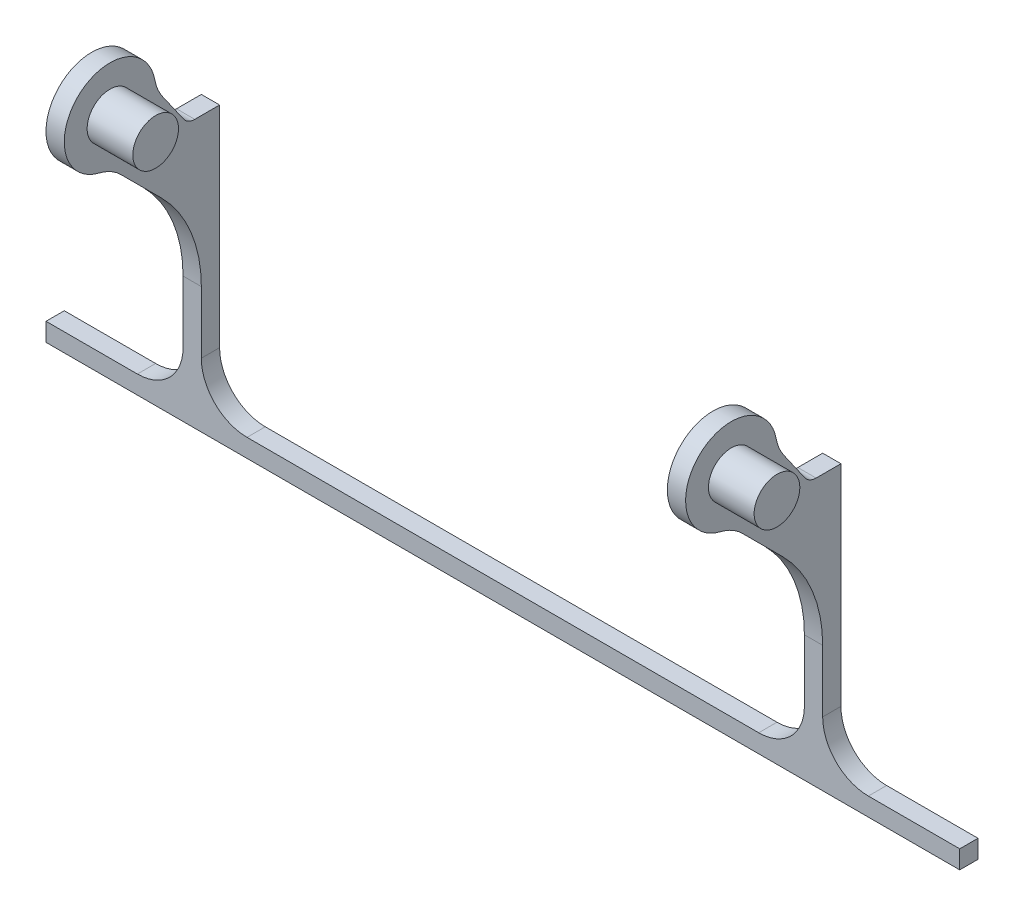
SolidWorks part; units mm, degrees
ref_plane "Plan de face" through (0, 0, 0) normal (0, 0, 1) x (1, 0, 0)
ref_plane "Plan de dessus" through (0, 0, 0) normal (0, 1, 0) x (1, 0, 0)
ref_plane "Plan de droite" through (0, 0, 0) normal (1, 0, 0) x (0, 0, -1)
sketch "Esquisse1" plane through (0, 0, 0) normal (0, 0, 1) x (1, 0, 0)
  line L0 (-100, -100) -> (100, -100) construction
  line L1 (100, -100) -> (100, -160) construction
  line L2 (100, -160) -> (-100, -160) construction
  line L3 (-100, -160) -> (-100, -100) construction
  line L4 (-100, -160) -> (-100, -156) construction
  line L5 (-100, -156) -> (-70, -156) construction
  line L6 (-70, -156) -> (-70, -100) construction
  line L7 (-70, -100) -> (-66, -100) construction
  line L8 (-66, -100) -> (-66, -156) construction
  line L9 (-66, -156) -> (66, -156) construction
  line L10 (66, -156) -> (66, -100) construction
  line L11 (66, -100) -> (70, -100) construction
  line L12 (70, -100) -> (70, -156) construction
  line L13 (70, -156) -> (100, -156) construction
  line L14 (-100, -97.7507) -> (-100, -110) construction
  line L15 (-100, 100) -> (-100, -100) construction
  line L16 (-100, -110) -> (-70, -110) construction
  line L17 (-70, -110) -> (-66, -110) construction
  line L18 (-66, -110) -> (66, -110) construction
  line L19 (66, -110) -> (70, -110) construction
  line L20 (70, -110) -> (100, -110) construction
  line L21 (-70, -110) -> (-66, -110)
  line L22 (-66, -110) -> (-66, -156)
  line L23 (-66, -156) -> (66, -156)
  line L24 (66, -156) -> (66, -110)
  line L25 (66, -110) -> (70, -110)
  line L26 (70, -110) -> (70, -156)
  line L27 (70, -156) -> (100, -156)
  line L28 (100, -156) -> (100, -160)
  line L29 (100, -160) -> (-100, -160)
  line L30 (-100, -160) -> (-100, -156)
  line L31 (-100, -156) -> (-70, -156)
  line L32 (-70, -156) -> (-70, -110)
  dimension "D1" = 4
  dimension "D2" = 4
  dimension "D3" = 4
  dimension "D4" = 4
  dimension "D5" = 4
  dimension "D6" = 30
  dimension "D7" = 30
  dimension "D8" = 10
  dimension "D9" = 60
extrude "Boss.-Extru.1" add sketch "Esquisse1" against normal blind 4
sketch "Esquisse2" plane through (70, 0, 0) normal (1, 0, 0) x (0, 0, -1)
  line L0 (0, -110) -> (-20, -110) construction
  line L1 (-20, -110) -> (-20, -90) construction
  line L2 (4, -110) -> (-10, -90) construction
  line L3 (0, -110) -> (0, -120) construction
  line L4 (0, -156) -> (0, -110) construction
  line L5 (0, -120) -> (-20, -100) construction
  line L6 (0, -120) -> (-20, -100)
  line L7 (4, -110) -> (-10, -90)
  line L8 (0, -120) -> (0, -110)
  line L9 (0, -110) -> (4, -110)
  arc A0 (-10, -90) -> (-20, -100) centre (-20, -90) ccw
  dimension "D3" = 20
  dimension "D1" = 20
  dimension "D2" = 20
  dimension "D4" = 10
extrude "Boss.-Extru.2" add sketch "Esquisse2" against normal blind 4
sketch "Esquisse3" plane through (-70, 0, 0) normal (-1, 0, 0) x (0, 0, 1)
  line L0 (-4, -110) -> (10, -90) construction
  line L1 (20, -100) -> (0, -120) construction
  line L2 (-4, -110) -> (10, -90)
  line L3 (20, -100) -> (0, -120)
  line L4 (-4, -110) -> (0, -110)
  line L5 (0, -110) -> (0, -120)
  arc A0 (20, -100) -> (10, -90) centre (20, -90) ccw construction
  arc A1 (20, -100) -> (10, -90) centre (20, -90) ccw
extrude "Boss.-Extru.3" add sketch "Esquisse3" against normal blind 4
fillet "Congé1" radius 30 2 edges at (68, -120, 0) (-68, -120, 0)
fillet "Congé2" radius 30 2 edges at (-68, -110, -4) (68, -110, -4)
fillet "Congé3" radius 10 4 edges at (66, -156, -2) (-66, -156, -2) (-70, -156, -2) (70, -156, -2)
sketch "Esquisse4" plane through (-70, 0, 0) normal (-1, 0, 0) x (0, 0, 1)
  line L0 (-4, -119.4567) -> (-4, -100)
  line L1 (-4, -100) -> (3, -100)
  line L2 (10, -90) -> (1.423, -102.2528) construction
  line L3 (3, -100) -> (-4, -119.4567)
extrude "Boss.-Extru.4" add sketch "Esquisse4" against normal blind 4
ref_plane "Plan1" through (-66, -100, 3) normal (0, 0, -1) x (-1, 0, 0)
sketch "Esquisse6" plane through (70, 0, 0) normal (1, 0, 0) x (0, 0, -1)
  line L0 (4, -119.4567) -> (4, -100)
  line L1 (4, -100) -> (-3, -100)
  line L2 (-3, -100) -> (4, -119.4567)
extrude "Boss.-Extru.5" add sketch "Esquisse6" against normal blind 4
sketch "Esquisse7" plane through (70, 0, 0) normal (1, 0, 0) x (0, 0, -1)
  line L0 (4, -100) -> (-20, -100) construction
  line L1 (-20, -100) -> (-20, -90) construction
  circle A0 centre (-20, -90) radius 5
  dimension "D1" = 10
extrude "Boss.-Extru.6" add sketch "Esquisse7" along normal blind 10
sketch "Esquisse9" plane through (-70, 0, 0) normal (-1, 0, 0) x (0, 0, 1)
  line L0 (-4, -100) -> (20, -100) construction
  line L1 (20, -100) -> (20, -90) construction
  circle A0 centre (20, -90) radius 5
  dimension "D1" = 10
extrude "Boss.-Extru.7" add sketch "Esquisse9" against normal blind 14
fillet "Congé4" radius 10 4 edges at (-68, -100, 20) (-68, -90, 10) (68, -90, 10) (68, -100, 20)
fillet "Congé5" radius 3 2 edges at (-68, -100, 3) (68, -100, 3)
